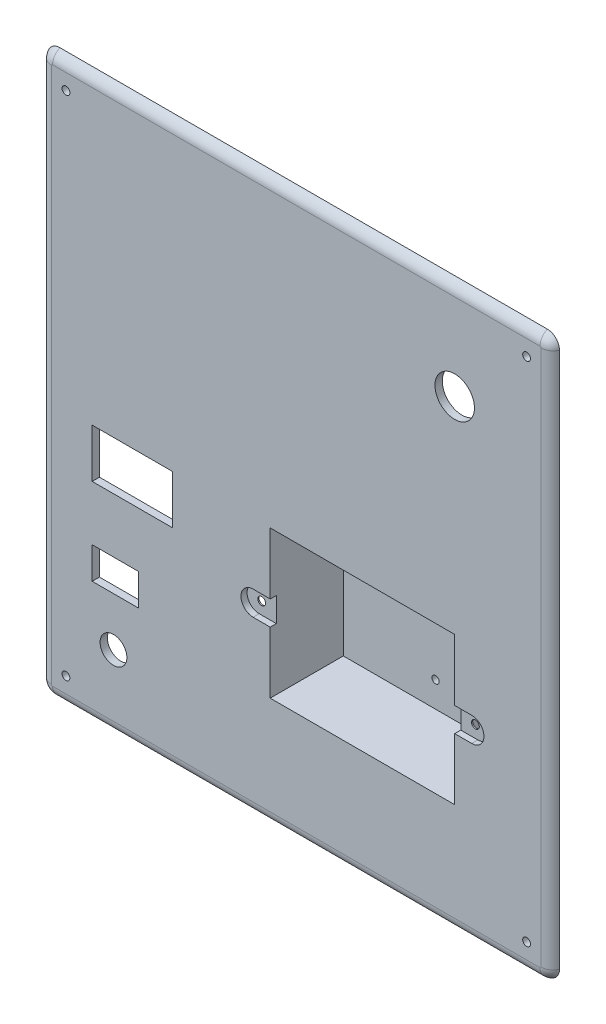
SolidWorks part; units mm, degrees
ref_plane "Front Plane" through (0, 0, 0) normal (0, 0, 1) x (1, 0, 0)
ref_plane "Top Plane" through (0, 0, 0) normal (0, 1, 0) x (1, 0, 0)
ref_plane "Right Plane" through (0, 0, 0) normal (1, 0, 0) x (0, 0, -1)
sketch "Sketch1" plane through (0, 0, 0) normal (0, 0, 1) x (1, 0, 0)
  line L0 (105, 230) -> (105, 0) construction
  line L1 (5, 0) -> (205, 0)
  line L2 (0, 5) -> (0, 225)
  line L3 (5, 230) -> (205, 230)
  line L4 (210, 5) -> (210, 225)
  line L5 (0, 115) -> (210, 115) construction
  line L7 (21.25, 63) -> (40.25, 63)
  line L8 (21.25, 63) -> (21.25, 50)
  line L9 (21.25, 50) -> (40.25, 50)
  line L10 (40.25, 63) -> (40.25, 50)
  line L11 (94.3, 105.5) -> (170, 105.5)
  line L12 (94.3, 105.5) -> (94.3, 45)
  line L13 (94.3, 45) -> (170, 45)
  line L14 (170, 105.5) -> (170, 45)
  line L15 (21.25, 105.5) -> (54.25, 105.5)
  line L16 (21.25, 105.5) -> (21.25, 85.5)
  line L17 (21.25, 85.5) -> (54.25, 85.5)
  line L18 (54.25, 105.5) -> (54.25, 85.5)
  arc A0 (5, 0) -> (0, 5) centre (5, 5) cw
  arc A1 (205, 0) -> (210, 5) centre (205, 5) ccw
  arc A2 (210, 225) -> (205, 230) centre (205, 225) ccw
  arc A3 (5, 230) -> (0, 225) centre (5, 225) ccw
  circle A4 centre (10.5, 219) radius 1.6
  circle A5 centre (10.5, 11) radius 1.6
  circle A6 centre (199.5, 11) radius 1.6
  circle A7 centre (199.5, 219) radius 1.6
  circle A8 centre (170, 190) radius 8.1
  circle A9 centre (30, 30) radius 5.5
  point P7 (0, 0)
  point P10 (210, 0)
  dimension "D3" = 5
  dimension "D6" = 3.2
  dimension "D9" = 16.2
  dimension "D10" = 11
  dimension "D1" = 210
  dimension "D2" = 230
  dimension "D4" = 10.5
  dimension "D5" = 11
  dimension "D7" = 19
  dimension "D8" = 13
  dimension "D11" = 30
  dimension "D12" = 20
  dimension "D13" = 30
  dimension "D14" = 21.25
  dimension "D15" = 40
  dimension "D16" = 40
  dimension "D17" = 60.5
  dimension "D18" = 75.7
  dimension "D19" = 45
  dimension "D20" = 40
  dimension "D21" = 20
  dimension "D22" = 33
extrude "Boss-Extrude1" add sketch "Sketch1" along normal blind 3
sketch "Sketch2" plane through (0, 0, 0) normal (0, 0, -1) x (-1, 0, 0)
  line L1 (-170, 45) -> (-94.3, 45)
  line L2 (-170, 45) -> (-170, 105.5)
  line L3 (-170, 105.5) -> (-94.3, 105.5)
  line L4 (-94.3, 45) -> (-94.3, 105.5)
  line L5 (-173, 42) -> (-91.3, 42)
  line L6 (-173, 42) -> (-173, 108.5)
  line L7 (-173, 108.5) -> (-91.3, 108.5)
  line L8 (-91.3, 42) -> (-91.3, 108.5)
  dimension "D1" = 3
  dimension "D2" = 3
  dimension "D3" = 3
  dimension "D4" = 3
extrude "Boss-Extrude2" add sketch "Sketch2" along normal blind 30
sketch "Sketch3" plane through (0, 0, -30) normal (0, 0, -1) x (-1, 0, 0)
  line L0 (-132.15, 105.5) -> (-132.15, 45) construction
  line L1 (-170, 105.5) -> (-94.3, 105.5)
  line L2 (-170, 105.5) -> (-170, 45)
  line L3 (-170, 45) -> (-94.3, 45)
  line L4 (-94.3, 105.5) -> (-94.3, 45)
  line L5 (-170, 75.25) -> (-94.3, 75.25) construction
  circle A0 centre (-132.15, 95) radius 1.5
  circle A1 centre (-132.15, 55.5) radius 1.5
  dimension "D1" = 3
  dimension "D2" = 10.5
extrude "Boss-Extrude3" add sketch "Sketch3" against normal blind 3 separate body
sketch "Sketch4" plane through (94.3, 0, 0) normal (1, 0, 0) x (0, 0, -1)
  line L0 (-3, 105.5) -> (30, 105.5) construction
  line L1 (27, 45) -> (27, 105.5) construction
  circle A0 centre (23, 85.5) radius 3
  dimension "D3" = 6
  dimension "D1" = 20
  dimension "D2" = 4
extrude "Cut-Extrude1" cut sketch "Sketch4" against normal blind 3
fillet "Fillet1" radius 5 8 edges at (208.5355, 228.5355, 3) (210, 115, 3) (208.5355, 1.4645, 3) (105, 0, 3) (1.4645, 1.4645, 3) (0, 115, 3) (1.4645, 228.5355, 3) (105, 230, 3)
sketch "Sketch5" plane through (0, 0, 3) normal (0, 0, 1) x (1, 0, 0)
  line L0 (94.3, 75.25) -> (170, 75.25) construction
  line L1 (94.3, 45) -> (94.3, 105.5) construction
  line L2 (170, 105.5) -> (170, 45) construction
  line L3 (94.3, 80.25) -> (87.3, 80.25)
  line L4 (87.3, 70.25) -> (94.3, 70.25)
  line L5 (94.3, 105.5) -> (94.3, 45) construction
  line L6 (87.3, 75.25) -> (94.3, 75.25) construction
  line L7 (132.15, 105.5) -> (132.15, 45) construction
  line L8 (94.3, 105.5) -> (170, 105.5) construction
  line L9 (170, 45) -> (94.3, 45) construction
  line L10 (94.3, 80.25) -> (94.3, 70.25)
  line L11 (170, 80.25) -> (177, 80.25)
  line L12 (177, 70.25) -> (170, 70.25)
  line L13 (170, 80.25) -> (170, 70.25)
  arc A0 (87.3, 80.25) -> (87.3, 70.25) centre (87.3, 75.25) ccw
  arc A1 (177, 80.25) -> (177, 70.25) centre (177, 75.25) cw
  dimension "D1" = 10
  dimension "D2" = 7
extrude "Cut-Extrude2" cut sketch "Sketch5" against normal blind 2.5
sketch "Sketch6" plane through (0, 0, 0.5) normal (0, 0, 1) x (1, 0, 0)
  line L0 (94.3, 75.25) -> (82.3, 75.25) construction
  line L1 (94.3, 45) -> (94.3, 105.5) construction
  line L2 (132.15, 105.5) -> (132.15, 45) construction
  line L3 (170, 105.5) -> (94.3, 105.5) construction
  line L4 (170, 45) -> (94.3, 45) construction
  arc A0 (87.3, 80.25) -> (87.3, 70.25) centre (87.3, 75.25) ccw construction
  circle A1 centre (88.3, 75.25) radius 1.6
  circle A2 centre (176, 75.25) radius 1.6
  dimension "D1" = 3.2
extrude "Cut-Extrude3" cut sketch "Sketch6" against normal through all
